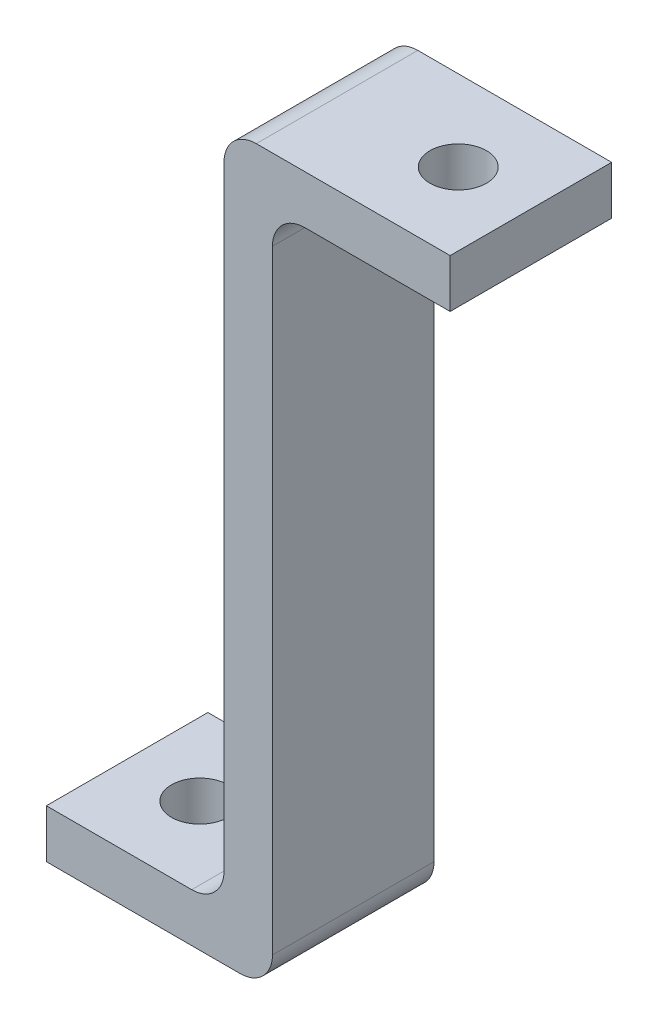
SolidWorks part; units mm, degrees
ref_plane "Front Plane" through (0, 0, 0) normal (0, 0, 1) x (1, 0, 0)
ref_plane "Top Plane" through (0, 0, 0) normal (0, 1, 0) x (1, 0, 0)
ref_plane "Right Plane" through (0, 0, 0) normal (1, 0, 0) x (0, 0, -1)
sketch "Sketch1" plane through (0, 0, 0) normal (0, 0, 1) x (1, 0, 0)
  line L0 (0, 0) -> (14, 0)
  line L1 (14, 0) -> (14, 42)
  line L2 (14, 42) -> (25, 42)
  line L3 (25, 42) -> (25, 45)
  line L4 (25, 45) -> (11, 45)
  line L5 (11, 45) -> (11, 3)
  line L6 (11, 3) -> (0, 3)
  line L7 (0, 3) -> (0, 0)
  dimension "D1" = 3
  dimension "D2" = 3
  dimension "D3" = 11
  dimension "D4" = 3
  dimension "D5" = 11
  dimension "D6" = 42
extrude "Boss-Extrude1" add sketch "Sketch1" against normal blind 10
fillet "Fillet1" radius 2 4 edges at (14, 0, -5) (11, 45, -5) (11, 3, -5) (14, 42, -5)
hole_wizard "Ø3.0mm Dowel Hole1" positions "3DSketch1" profile "Sketch2" hole size "Ø3.0" standard "ANSI Metric" end condition through all
sketch3d "3DSketch1"
  line L0 (0, 0, -5) -> (12, 0, -5) construction
  line L1 (0, 0, -10) -> (0, 0, 0) construction
  line L2 (12, 0, -10) -> (12, 0, 0) construction
  line L4 (4.5, 0, -5) -> (4.5, 0, -10) construction
  line L6 (0, 0, -10) -> (12, 0, -10) construction
  point P0 (4.5, 0, -5)
  dimension "D1" = 4.5
sketch "Sketch2" plane through (4.5, 0, -5) normal (1, 0, 0) x (0, 0, -1)
  line L0 (0, 0) -> (0, 45)
  line L1 (0, 45) -> (1.75, 45)
  line L2 (1.75, 45) -> (1.75, 0)
  line L5 (1.75, 0) -> (0, 0)
  line L11 (0, -6.35) -> (0, 107.95) construction
  dimension "Thru Hole Dia." = 3.5
  dimension "Thru Hole Depth" = 45
hole_wizard "Ø3.0mm Dowel Hole2" positions "Sketch3" profile "Sketch4" hole size "Ø3.0" standard "ANSI Metric" end condition through all
sketch "Sketch3" plane through (0, 45, 0) normal (0, 1, 0) x (1, 0, 0)
  line L0 (25, 5) -> (13, 5) construction
  line L1 (25, 10) -> (25, 0) construction
  line L2 (13, 10) -> (13, 0) construction
  line L4 (20.5, 5) -> (20.5, 10) construction
  line L5 (25, 10) -> (13, 10) construction
  point P0 (20.5, 5)
  dimension "D1" = 4.5
sketch "Sketch4" plane through (20.5, 45, -5) normal (1, 0, 0) x (0, 0, 1)
  line L0 (0, 0) -> (0, 45)
  line L1 (0, 45) -> (1.75, 45)
  line L2 (1.75, 45) -> (1.75, 0)
  line L5 (1.75, 0) -> (0, 0)
  line L11 (0, -6.35) -> (0, 107.95) construction
  dimension "Thru Hole Dia." = 3.5
  dimension "Thru Hole Depth" = 45
